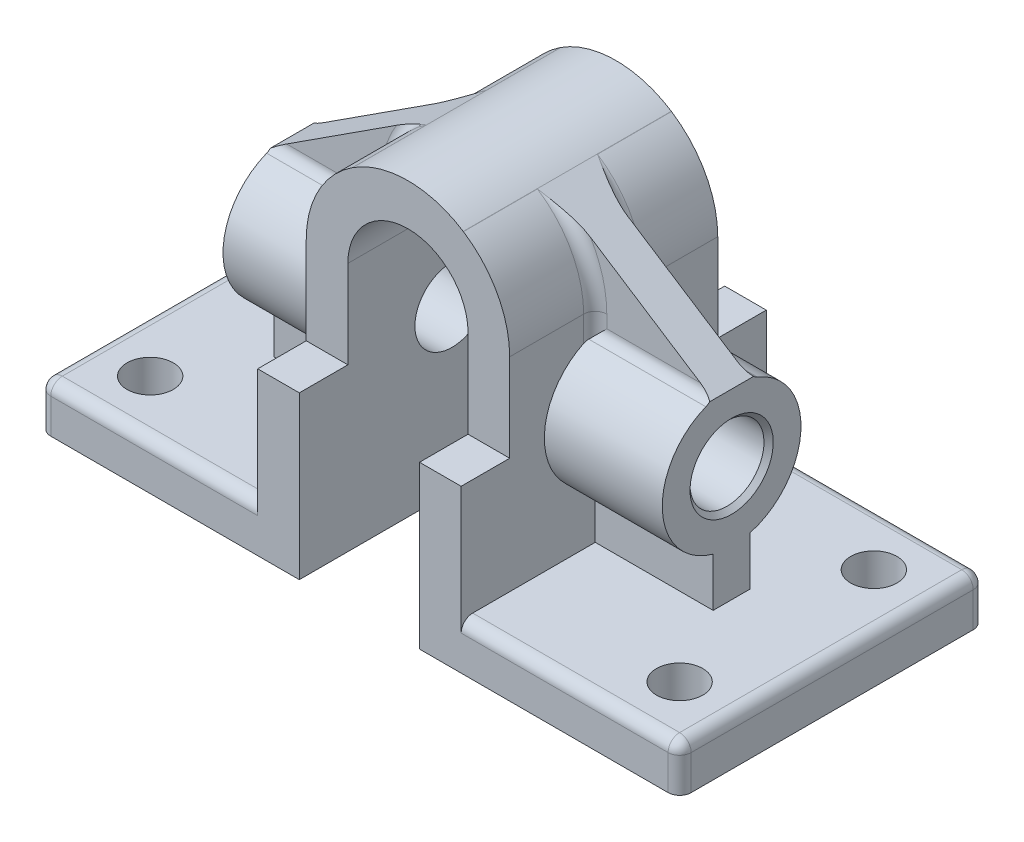
SolidWorks part; units mm, degrees
ref_plane "Спереди" through (0, 0, 0) normal (0, 0, 1) x (1, 0, 0)
ref_plane "Сверху" through (0, 0, 0) normal (0, 1, 0) x (1, 0, 0)
ref_plane "Справа" through (0, 0, 0) normal (1, 0, 0) x (0, 0, -1)
sketch "Эскиз1" plane through (0, 0, 0) normal (0, 0, 1) x (1, 0, 0)
  line L0 (0, 0) -> (0, 92.4547) construction
  line L3 (32.6699, 0) -> (-32.6699, 0) construction
  line L4 (0, 0) -> (0, -91.7652) construction
  line L5 (69.2568, -54) -> (13, -54)
  line L7 (69.2568, -44) -> (22, -44)
  line L8 (-69.2568, -44) -> (-69.2568, -54)
  line L9 (69.2568, -44) -> (69.2568, -54)
  line L10 (-22, 0) -> (-22, -44)
  line L11 (-13, 0) -> (-13, -54)
  line L12 (13, 0) -> (13, -54)
  line L13 (22, 0) -> (22, -44)
  line L14 (-22, -44) -> (-69.2568, -44)
  line L15 (-13, -54) -> (-69.2568, -54)
  arc A2 (13, 0) -> (-13, 0) centre (0, 0) ccw
  arc A3 (22, 0) -> (-22, 0) centre (0, 0) ccw
  point P9 (0, 0)
  point P13 (0, -54)
  point P20 (0, 0)
  point P21 (0, 0)
  dimension "D4" = 69.2568
  dimension "D6" = 10
  dimension "D1" = 13
  dimension "D2" = 22
  dimension "D3" = 138.5135
  dimension "D5" = 54
  dimension "D10" = 54
extrude "Бобышка-Вытянуть1" add sketch "Эскиз1" along normal blind 33 and the other way blind 33
sketch "Эскиз5" plane through (-22, 0, 0) normal (-1, 0, 0) x (0, 0, 1)
  line L0 (38.3684, 0) -> (-38.3684, 0) construction
  line L2 (0, 76.8855) -> (0, -76.8855) construction
  line L3 (-33, -19) -> (-22.5, -19)
  line L4 (-33, 0) -> (-33, -44) construction
  line L5 (33, 0) -> (33, -44) construction
  line L6 (-22.5, 22) -> (-22.5, -19)
  line L7 (33, 22) -> (-33, 22) construction
  line L8 (22.5, 22) -> (22.5, -19)
  line L9 (-33, -54) -> (33, -54) construction
  line L12 (-22.5, 22) -> (-33, 22)
  line L13 (-33, 22) -> (-33, 0) construction
  line L14 (-33, 22) -> (-33, -19)
  line L15 (22.5, 22) -> (33, 22)
  line L16 (33, 22) -> (33, -19)
  line L17 (22.5, -19) -> (33, -19)
  point P3 (0, 0)
  point P7 (0, 0)
  dimension "D1" = 35
  dimension "D2" = 22.5
  dimension "D3" = 45
extrude "Вырез-Вытянуть1" cut sketch "Эскиз5" against normal up to vertex (44 mm away) up to point (22, 0, -33)
sketch "Эскиз6" plane through (-22, 0, 0) normal (-1, 0, 0) x (0, 0, 1)
  line L0 (0, 0) -> (0, -76.0057) construction
  line L1 (-22.5, -19) -> (22.5, -19) construction
  line L2 (-4, 22) -> (-4, -44)
  line L3 (22.5, 22) -> (-22.5, 22) construction
  line L4 (-33, -44) -> (33, -44) construction
  line L5 (4, 22) -> (4, -44)
  line L6 (-33, -44) -> (33, -44) construction
  line L7 (0, 0) -> (0, 22) construction
  line L8 (-4, -44) -> (4, -44)
  line L9 (-4, 22) -> (4, 22)
  circle A3 centre (0, -19) radius 15
  dimension "D2" = 30
  dimension "D3" = 8
  dimension "D1" = 4
extrude "Бобышка-Вытянуть2" add sketch "Эскиз6" along normal blind 25.5 and the other way blind 69.5 contours A3
extrude "Бобышка-Вытянуть4" add sketch "Эскиз6<5>" along normal blind 25.5 and the other way blind 69.5 contours L5 L8 L2 L9
sketch "Эскиз6<5>" plane through (-22, 0, 0) normal (-1, 0, 0) x (0, 0, 1) same geometry as "Эскиз6"
sketch "Эскиз9" plane through (0, 0, -33) normal (0, 0, -1) x (-1, 0, 0)
  line L0 (-47.5, -4.5432) -> (-47.5, 28.0612)
  line L1 (-47.5, 28.0612) -> (47.5, 28.0612)
  line L3 (47.5, 28.0612) -> (47.5, -4.5432)
  line L4 (47.5, 22) -> (47.5, -4.5432) construction
  line L5 (-47.5, -4.5432) -> (-11.9558, 18.4677)
  line L6 (47.5, -4.5432) -> (11.9558, 18.4677)
  line L7 (-13, 0) -> (-13, -54)
  line L8 (-13, -54) -> (13, -54)
  line L9 (13, -54) -> (13, 0)
  arc A1 (13, 0) -> (-13, 0) centre (0, 0) ccw
  arc A4 (11.9558, 18.4677) -> (-11.9558, 18.4677) centre (0, 0) ccw
extrude "Вырез-Вытянуть2" cut sketch "Эскиз9" against normal blind 62.5
sketch "Эскиз10" plane through (-47.5, 0, 0) normal (-1, 0, 0) x (0, 0, 1)
  line L0 (-22.5, -19) -> (22.5, -19) construction
  circle A0 centre (0, -19) radius 8
  dimension "D1" = 16
extrude "Вырез-Вытянуть3" cut sketch "Эскиз10" against normal up to vertex (95 mm away) up to point (47.5, -4.5432, -4)
chamfer "Фаска1" distance 1 2 edges at (-47.5, -27, 0) (47.5, -27, 0)
fillet "Скругление1" radius 2.5 10 edges at (-45.6284, -44, 33) (-69.2568, -49, 33) (-69.2568, -44, 0) (-69.2568, -49, -33) (-45.6284, -44, -33) (69.2568, -49, -33) (69.2568, -49, 33) (45.6284, -44, -33) (69.2568, -44, 0) (45.6284, -44, 33)
fillet "Скругление3" radius 2.5 12 edges at (19.339, 10.4882, 4) (19.339, 10.4882, -4) (22, -2.2716, -4) (34.75, -4.5432, -4) (22, -2.2716, 4) (34.75, -4.5432, 4) (-19.339, 10.4882, 4) (-22, -2.2716, 4) (-34.75, -4.5432, 4) (-34.75, -4.5432, -4) (-22, -2.2716, -4) (-19.339, 10.4882, -4)
sketch "Эскиз11" plane through (0, -54, 0) normal (0, -1, 0) x (1, 0, 0)
  line L0 (-67.0673, 21) -> (-57.2568, 21) construction
  line L1 (-57.2568, 31.5148) -> (-57.2568, 24.6324) construction
  line L2 (-66.7568, 33) -> (-13, 33) construction
  line L3 (-69.2568, -30.5) -> (-69.2568, 30.5) construction
  line L4 (-61.514, 21) -> (-53.6824, 21) construction
  line L5 (-57.2568, 24.6324) -> (-57.2568, 17.1805) construction
  line L6 (0, -45.2738) -> (0, 45.2738) construction
  line L8 (80.5712, 0) -> (-80.5712, 0) construction
  circle A0 centre (-57.2568, 21) radius 5
  circle A1 centre (57.2568, 21) radius 5
  circle A2 centre (57.2568, -21) radius 5
  circle A3 centre (-57.2568, -21) radius 5
  point P16 (0, 0)
  point P20 (0, 0)
  dimension "D3" = 10
  dimension "D1" = 12
  dimension "D2" = 12
extrude "Вырез-Вытянуть4" cut sketch "Эскиз11" against normal up to vertex (10 mm away) up to point (-22, -44, 4)
